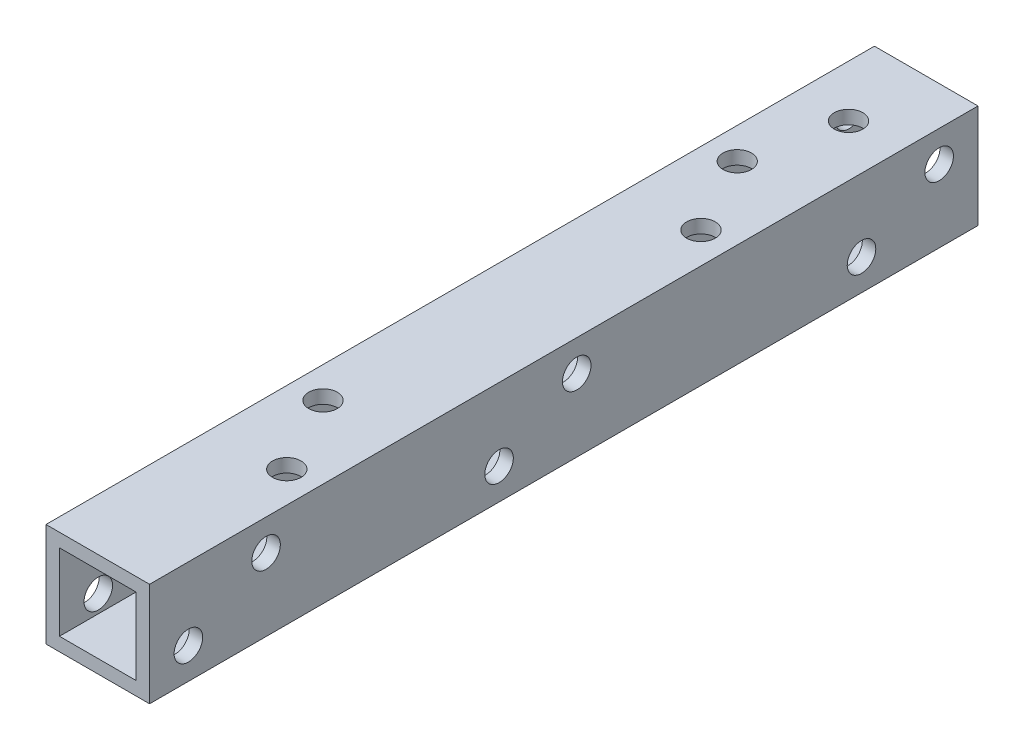
SolidWorks part; units mm, degrees
material "6061-T4 (SS)"
ref_plane "Front Plane" through (0, 0, 0) normal (1, 0, 0) x (0, 1, 0)
ref_plane "Top Plane" through (0, 0, 0) normal (0, 0, 1) x (0, 1, 0)
ref_plane "Right Plane" through (0, 0, 0) normal (0, 1, 0) x (-1, 0, 0)
sketch "Sketch1" plane through (0, 0, 0) normal (0, 0, 1) x (0, 1, 0)
  line L1 (6.35, -6.35) -> (-6.35, -6.35)
  line L2 (6.35, -6.35) -> (6.35, 6.35)
  line L3 (6.35, 6.35) -> (-6.35, 6.35)
  line L4 (-6.35, -6.35) -> (-6.35, 6.35)
  line L5 (6.35, -6.35) -> (-6.35, 6.35) construction
  line L6 (6.35, 6.35) -> (-6.35, -6.35) construction
  line L7 (4.699, -4.699) -> (-4.699, -4.699)
  line L8 (4.699, -4.699) -> (4.699, 4.699)
  line L9 (4.699, 4.699) -> (-4.699, 4.699)
  line L10 (-4.699, -4.699) -> (-4.699, 4.699)
  line L11 (4.699, -4.699) -> (-4.699, 4.699) construction
  line L12 (4.699, 4.699) -> (-4.699, -4.699) construction
  point P0 (0, 0)
  point P6 (0, 0)
  dimension "D1" = 12.7
  dimension "D2" = 1.651
extrude "Boss-Extrude1" add sketch "Sketch1" along normal blind 101.6
sketch "Sketch2" plane through (0, 6.35, 0) normal (0, 1, 0) x (-1, 0, 0)
  line L0 (-6.35, 50.8) -> (6.35, 50.8) construction
  line L1 (-6.35, 101.6) -> (-6.35, 0) construction
  line L2 (6.35, 101.6) -> (6.35, 0) construction
  line L3 (-6.35, 101.6) -> (6.35, 101.6) construction
  line L12 (2.54, 20.6375) -> (-2.54, 20.6375) construction
  line L15 (2.54, 71.4375) -> (-2.54, 71.4375) construction
  line L16 (2.54, 71.4375) -> (2.54, 80.9625) construction
  line L17 (2.54, 80.9625) -> (-2.54, 80.9625) construction
  line L18 (-2.54, 71.4375) -> (-2.54, 80.9625) construction
  line L19 (2.54, 71.4375) -> (-2.54, 80.9625) construction
  line L20 (2.54, 80.9625) -> (-2.54, 71.4375) construction
  line L21 (2.54, 20.6375) -> (2.54, 30.1625) construction
  line L22 (2.54, 30.1625) -> (-2.54, 30.1625) construction
  line L23 (-2.54, 20.6375) -> (-2.54, 30.1625) construction
  line L24 (2.54, 20.6375) -> (-2.54, 30.1625) construction
  line L25 (2.54, 30.1625) -> (-2.54, 20.6375) construction
  circle A4 centre (-2.54, 80.9625) radius 1.75
  circle A5 centre (2.54, 71.4375) radius 1.75
  circle A6 centre (-2.54, 30.1625) radius 1.75
  circle A7 centre (2.54, 20.6375) radius 1.75
  point P7 (0, 101.6)
  point P8 (0, 25.4)
  point P10 (0, 76.2)
  dimension "D2" = 25.4
  dimension "D13" = 3.5
  dimension "D3" = 5.08
  dimension "D4" = 9.525
  dimension "D5" = 25.4
  dimension "D11" = 5.08
  dimension "D12" = 9.525
extrude "Cut-Extrude1" cut sketch "Sketch2" against normal blind 22.2885
sketch "Sketch3" plane through (6.35, 0, 0) normal (1, 0, 0) x (0, 1, 0)
  line L1 (2.54, 4.7625) -> (-2.54, 4.7625) construction
  line L2 (2.54, 4.7625) -> (2.54, 14.2875) construction
  line L7 (2.54, 14.2875) -> (-2.54, 14.2875) construction
  line L11 (-2.54, 4.7625) -> (-2.54, 14.2875) construction
  line L13 (2.54, 4.7625) -> (-2.54, 14.2875) construction
  line L18 (2.54, 14.2875) -> (-2.54, 4.7625) construction
  line L20 (2.54, 87.3125) -> (-2.54, 87.3125) construction
  line L21 (2.54, 87.3125) -> (2.54, 96.8375) construction
  line L22 (2.54, 96.8375) -> (-2.54, 96.8375) construction
  line L23 (-2.54, 87.3125) -> (-2.54, 96.8375) construction
  line L24 (2.54, 87.3125) -> (-2.54, 96.8375) construction
  line L25 (2.54, 96.8375) -> (-2.54, 87.3125) construction
  line L26 (-6.35, 101.6) -> (6.35, 101.6) construction
  line L27 (2.54, 49.2125) -> (-2.54, 49.2125) construction
  line L28 (2.54, 49.2125) -> (2.54, 58.7375) construction
  line L29 (2.54, 58.7375) -> (-2.54, 58.7375) construction
  line L30 (-2.54, 49.2125) -> (-2.54, 58.7375) construction
  line L31 (2.54, 49.2125) -> (-2.54, 58.7375) construction
  line L32 (2.54, 58.7375) -> (-2.54, 49.2125) construction
  line L33 (-6.35, 0) -> (6.35, 0) construction
  circle A8 centre (-2.54, 14.2875) radius 1.75
  circle A9 centre (2.54, 4.7625) radius 1.75
  circle A10 centre (-2.54, 96.8375) radius 1.75
  circle A11 centre (2.54, 87.3125) radius 1.75
  circle A12 centre (-2.54, 58.7375) radius 1.75
  circle A13 centre (2.54, 49.2125) radius 1.75
  point P0 (0, 9.525)
  point P8 (0, 92.075)
  point P15 (0, 53.975)
  point P16 (0, 101.6)
  dimension "D4" = 3.5
  dimension "D7" = 3.5
  dimension "D11" = 3.5
  dimension "D1" = 5.08
  dimension "D2" = 9.525
  dimension "D3" = 9.525
  dimension "D5" = 5.08
  dimension "D6" = 9.525
  dimension "D8" = 9.525
  dimension "D9" = 5.08
  dimension "D10" = 9.525
  dimension "D12" = 53.975
extrude "Cut-Extrude2" cut sketch "Sketch3" against normal blind 22.098 contours A10 | A11 | A8 | A9 | A12 | A13 region at (6.35, -2.54, 14.2875) region at (6.35, 2.54, 4.7625) region at (6.35, -2.54, 96.8375) region at (6.35, 2.54, 87.3125) region at (6.35, -2.54, 58.7375) region at (6.35, 2.54, 49.2125)
sketch "Sketch4" plane through (0, 6.35, 0) normal (0, 1, 0) x (-1, 0, 0)
  line L0 (-6.35, 6.5125) -> (-6.35, 3.0125) construction
  line L1 (-6.35, 16.0375) -> (-6.35, 12.5375) construction
  line L2 (-6.35, 6.5125) -> (-6.35, 3.0125) construction
  line L3 (-6.35, 16.0375) -> (-6.35, 12.5375) construction
  line L4 (-6.35, 14.2875) -> (-6.35, 4.7625)
  circle A0 centre (0, 9.525) radius 1.75
  point P8 (-6.35, 9.525)
  point P9 (0, 0)
  point P10 (0, 0)
  point P11 (0, 0)
  point P13 (0, 0)
  dimension "D1" = 3.5
extrude "Cut-Extrude3" cut sketch "Sketch4" against normal blind 24.892 contours A0 region at (0, 6.35, 9.525)
